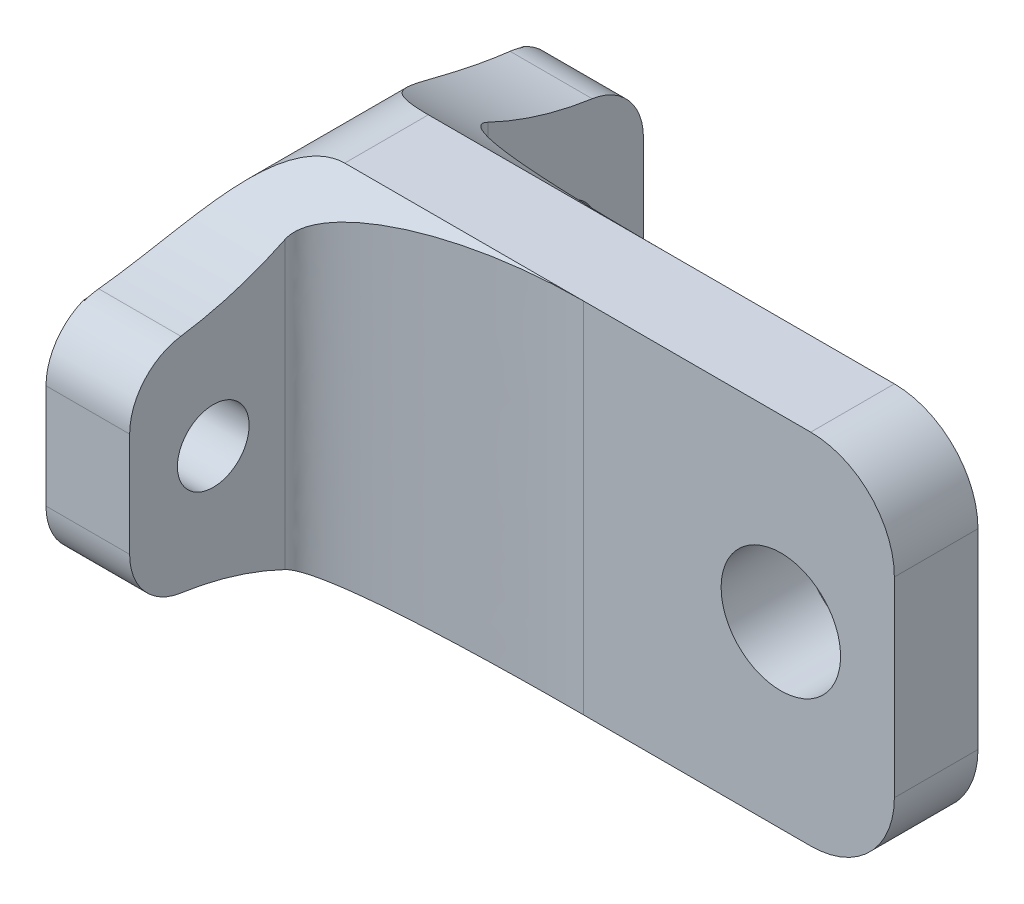
SolidWorks part; units mm, degrees
ref_plane "前视基准面" through (0, 0, 0) normal (0, 0, 1) x (1, 0, 0)
ref_plane "上视基准面" through (0, 0, 0) normal (0, 1, 0) x (1, 0, 0)
ref_plane "右视基准面" through (0, 0, 0) normal (1, 0, 0) x (0, 0, -1)
other "Configuration Table"
sketch "草图1" plane through (0, 0, 0) normal (0, 0, 1) x (1, 0, 0)
  line L1 (0, 0) -> (53, 0)
  line L2 (0, 0) -> (0, 30)
  line L3 (0, 30) -> (53, 30)
  line L4 (53, 0) -> (53, 30)
  dimension "D1" = 30
  dimension "D2" = 53
extrude "凸台-拉伸1" add sketch "草图1" along normal blind 7
sketch "草图2" plane through (0, 0, 0) normal (0, 0, -1) x (-1, 0, 0)
  line L0 (-53, 15) -> (0, 15) construction
  line L1 (-53, 0) -> (-53, 30) construction
  line L2 (0, 30) -> (0, 0) construction
  circle A0 centre (-43.5, 15) radius 5
  dimension "D1" = 10
  dimension "D2" = 43.5
extrude "切除-拉伸1" cut sketch "草图2" against normal up to next
fillet "圆角1" radius 7 4 edges at (53, 30, 3.5) (0, 30, 3.5) (0, 0, 3.5) (53, 0, 3.5)
sketch "草图3" plane through (0, 0, 7) normal (0, 0, 1) x (1, 0, 0)
  line L0 (0, 15) -> (20.808, 15) construction
  line L1 (0, 23) -> (0, 7) construction
  line L3 (0, 24) -> (7, 24)
  line L4 (0, 24) -> (0, 6)
  line L5 (0, 6) -> (7, 6)
  line L6 (7, 24) -> (7, 6)
  dimension "D1" = 18
  dimension "D2" = 9
  dimension "D3" = 7
extrude "凸台-拉伸2" add sketch "草图3" along normal blind 18
sketch "草图4" plane through (0, 0, 0) normal (0, 0, -1) x (-1, 0, 0)
  line L0 (0, 15) -> (-18.6209, 15) construction
  line L1 (0, 23) -> (0, 7) construction
  line L7 (0, 24) -> (-7, 24)
  line L8 (0, 24) -> (0, 6)
  line L9 (0, 6) -> (-7, 6)
  line L10 (-7, 24) -> (-7, 6)
  dimension "D1" = 18
  dimension "D2" = 9
  dimension "D3" = 7
extrude "凸台-拉伸3" add sketch "草图4" along normal blind 18
sketch "草图5" plane through (0, 0, 0) normal (-1, 0, 0) x (0, 0, 1)
  line L0 (-18, 15) -> (25, 15) construction
  line L1 (-18, 6) -> (-18, 24) construction
  line L2 (25, 24) -> (25, 6) construction
  circle A0 centre (-11, 15) radius 3
  circle A1 centre (18, 15) radius 3
  dimension "D1" = 6
  dimension "D2" = 6
  dimension "D3" = 7
  dimension "D4" = 7
extrude "切除-拉伸2" cut sketch "草图5" against normal up to next
fillet "圆角2" radius 20 2 edges at (7, 15, 7) (7, 15, 0)
fillet "圆角3" radius 30 4 edges
fillet "圆角4" radius 5 3 edges at (0.0359, 24, 25) (2.4099, 28.2849, 9.5489) (3.5359, 24, 25)
fillet "圆角5" radius 5 3 edges at (3.5359, 6, 25) (0.0359, 6, 25)
fillet "圆角6" radius 5 3 edges at (0.0359, 6, -18) (2.4099, 1.7151, -2.5489) (3.5359, 6, -18)
fillet "圆角7" radius 5 3 edges at (3.5359, 24, -18) (0.0359, 24, -18)
